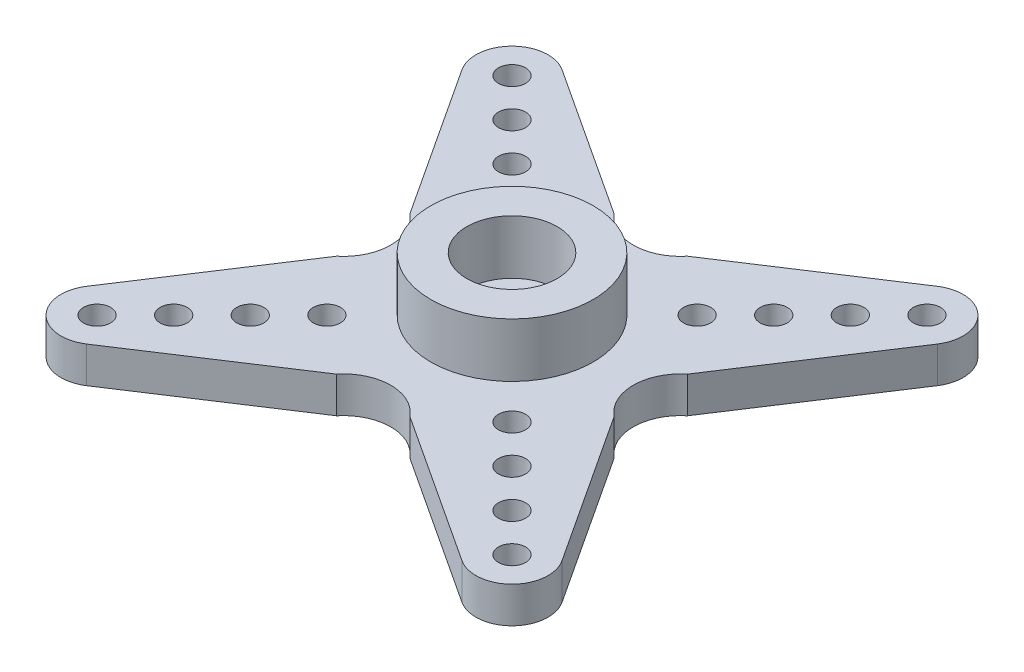
SolidWorks part; units mm, degrees
ref_plane "Front Plane" through (0, 0, 0) normal (0, 0, 1) x (1, 0, 0)
ref_plane "Top Plane" through (0, 0, 0) normal (0, 1, 0) x (1, 0, 0)
ref_plane "Right Plane" through (0, 0, 0) normal (1, 0, 0) x (0, 0, -1)
sketch "Sketch1" plane through (0, 0, 0) normal (0, 1, 0) x (1, 0, 0)
  line L1 (-15.7247, 4.7864) -> (10.0847, 4.7864) construction
  line L2 (-2.82, 4.7864) -> (-2.82, -21.023) construction
  line L3 (10.0847, -21.023) -> (-15.7247, -21.023) construction
  line L4 (10.0847, 4.7864) -> (10.0847, -21.023) construction
  line L5 (-10.5057, -6.0895) -> (-4.8488, -0.4326) construction
  line L6 (-15.7247, 4.7864) -> (10.0847, -21.023) construction
  line L7 (-16.2903, -8.1183) -> (10.0847, -8.1183) construction
  line L8 (10.3437, 2.2766) -> (4.8657, -6.0895)
  line L9 (7.5749, 5.0454) -> (-0.7912, -0.4326)
  line L10 (4.8657, -6.0895) -> (-0.7912, -0.4326) construction
  line L11 (-15.9837, -18.5132) -> (-10.5057, -10.1471)
  line L12 (-13.2149, -21.282) -> (-4.8488, -15.804)
  line L13 (-13.2149, 5.0454) -> (-4.8488, -0.4326)
  line L14 (-15.9837, 2.2766) -> (-10.5057, -6.0895)
  line L15 (-15.7247, -21.023) -> (10.0847, 4.7864) construction
  line L19 (7.5749, -21.282) -> (-0.7912, -15.804)
  line L20 (10.3437, -18.5132) -> (4.8657, -10.1471)
  circle A0 centre (-2.82, -8.1183) radius 6.7175 construction
  arc A1 (-10.5057, -6.0895) -> (-10.5057, -10.1471) centre (-12.1473, -8.1183) cw
  arc A2 (10.3437, -18.5132) -> (7.5749, -21.282) centre (8.6705, -19.6088) cw
  arc A3 (-15.9837, 2.2766) -> (-13.2149, 5.0454) centre (-14.3105, 3.3722) cw
  arc A4 (10.3437, 2.2766) -> (7.5749, 5.0454) centre (8.6705, 3.3722) ccw
  arc A5 (4.8657, -6.0895) -> (4.8657, -10.1471) centre (6.5073, -8.1183) ccw
  arc A6 (-15.9837, -18.5132) -> (-13.2149, -21.282) centre (-14.3105, -19.6088) ccw
  arc A7 (-0.7912, -15.804) -> (-4.8488, -15.804) centre (-2.82, -17.4456) ccw
  arc A8 (-0.7912, -0.4326) -> (-4.8488, -0.4326) centre (-2.82, 1.209) cw
  point P6 (10.0847, -8.1183)
  point P7 (-2.82, 4.7864)
  point P36 (-2.82, -1.4008)
  point P37 (3.8975, -8.1183)
  dimension "D2" = 2
  dimension "D3" = 9.5
  dimension "D1" = 36.5
  dimension "D4" = 8
  dimension "D5" = 10
  dimension "D6" = 90
extrude "Boss-Extrude1" add sketch "Sketch1" along normal blind 2
sketch "Sketch5" plane through (0, 2, 0) normal (0, 1, 0) x (1, 0, 0)
  circle A4 centre (-2.82, -8.1183) radius 4.5
  circle A5 centre (-2.82, -8.1183) radius 2.5
  circle A6 centre (-2.82, -8.1183) radius 6.7175 construction
  dimension "D1" = 9
  dimension "D2" = 5
extrude "Boss-Extrude2" add sketch "Sketch5" along normal blind 3
ref_axis "Axis1" through (-2.82, 5, 8.1183) along (0, -1, 0)
sketch "Sketch8" plane through (0, 0, 0) normal (0, -1, 0) x (1, 0, 0)
  circle A0 centre (-2.82, 8.1183) radius 1.5
  dimension "D1" = 3
extrude "Cut-Extrude2" cut sketch "Sketch8" against normal through all
sketch "Sketch9" plane through (0, 0, 0) normal (0, -1, 0) x (1, 0, 0)
  circle A0 centre (-2.82, 8.1183) radius 4.5
  circle A1 centre (-2.82, 8.1183) radius 3.3
  circle A2 centre (-2.82, 8.1183) radius 2.8
  circle M1 centre (-2.82, 8.1183) radius 1.5
  dimension "D1" = 9
  dimension "D2" = 1.2
  dimension "D3" = 0.5
sketch "Sketch10" plane through (0, 0, 0) normal (0, -1, 0) x (1, 0, 0)
  line L0 (-15.7247, 21.023) -> (10.0847, -4.7864) construction
  circle A0 centre (8.6705, -3.3722) radius 0.75
  dimension "D1" = 1.5
  dimension "D2" = 2
extrude "Cut-Extrude3" cut sketch "Sketch10" against normal up to next
pattern_linear "LPattern1" count 4 spacing 3 along (-0.7071, 0, 0.7071) of "Cut-Extrude3"
pattern_circular "CirPattern1" count 4 every 90 about axis through (-2.82, 5, 8.1183) along (0, -1, 0) of "LPattern1"
extrude "Cut-Extrude4" cut sketch "Sketch9" against normal blind 1 contours A0 A1 | A2 M1 region at (-7.1927, 0, 8.1183) region at (-5.5408, 0, 8.1183)
